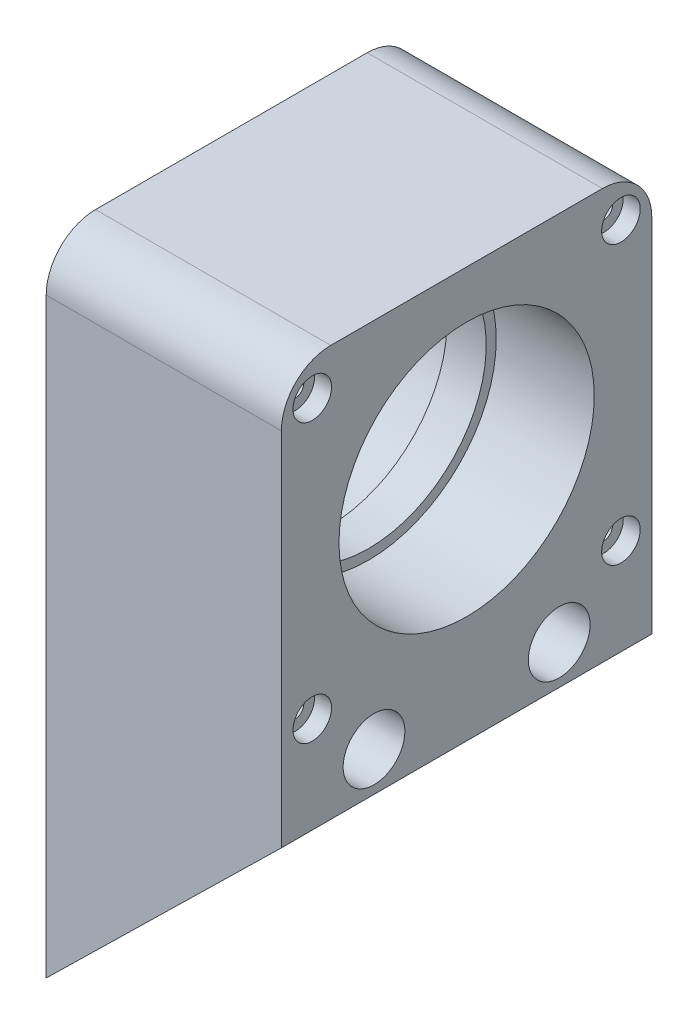
SolidWorks part; units mm, degrees
ref_plane "Front Plane" through (0, 0, 0) normal (0, 0, 1) x (1, 0, 0)
ref_plane "Top Plane" through (0, 0, 0) normal (0, 1, 0) x (1, 0, 0)
ref_plane "Right Plane" through (0, 0, 0) normal (1, 0, 0) x (0, 0, -1)
sketch "Sketch1" plane through (0, 0, 0) normal (0, 0, 1) x (1, 0, 0)
  line L0 (381, 457.2) -> (457.2, 457.2)
  line L1 (457.2, 457.2) -> (457.2, 431.8)
  line L2 (381, 457.2) -> (381, 357.2)
  line L5 (381, 357.2) -> (457.2, 431.8)
  dimension "D1" = 76.2
  dimension "D2" = 100
extrude "Boss-Extrude1" add sketch "Sketch1" along normal blind 120
sketch "Sketch3" plane through (457.2, 0, 0) normal (1, 0, 0) x (0, 0, -1)
  line L1 (-120, 431.8) -> (0, 431.8)
  line L2 (-120, 431.8) -> (-120, 357.2)
  line L3 (-120, 357.2) -> (0, 357.2)
  line L4 (0, 431.8) -> (0, 357.2)
  circle A0 centre (-90, 394.5) radius 4.25
  circle A1 centre (-30, 394.5) radius 4.25
  circle A2 centre (-90, 444.5) radius 4.25
  circle A3 centre (-30, 444.5) radius 4.25
  dimension "D1" = 30
  dimension "D2" = 30
  dimension "D3" = 37.3
  dimension "D4" = 37.3
extrude "Cut-Extrude1" cut sketch "Sketch3" against normal blind 120 contours A1 | A0
sketch "Sketch5" plane through (457.2, 0, 0) normal (1, 0, 0) x (0, 0, -1)
  circle A0 centre (-90, 394.5) radius 10
  circle A1 centre (-30, 394.5) radius 10
  circle A2 centre (-90, 444.5) radius 10
  circle A3 centre (-30, 444.5) radius 10
extrude "Cut-Extrude2" cut sketch "Sketch5" against normal blind 53
sketch "Sketch6" plane through (457.2, 0, 0) normal (1, 0, 0) x (0, 0, -1)
  circle A0 centre (-90, 444.5) radius 4.25
  circle A1 centre (-30, 444.5) radius 4.25
extrude "Cut-Extrude3" cut sketch "Sketch6" against normal blind 103
sketch "Sketch7" plane through (0, 457.2, 0) normal (0, 1, 0) x (1, 0, 0)
  line L1 (381, 0) -> (457.2, 0)
  line L2 (381, 0) -> (381, -120)
  line L3 (381, -120) -> (457.2, -120)
  line L4 (457.2, 0) -> (457.2, -120)
extrude "Boss-Extrude2" add sketch "Sketch7" along normal blind 101.6
sketch "Sketch8" plane through (381, 0, 0) normal (-1, 0, 0) x (0, 0, 1)
  line L0 (120, 457.2) -> (0, 457.2)
  line L1 (120, 558.8) -> (120, 357.2) construction
  line L2 (0, 558.8) -> (0, 357.2) construction
  line L3 (0, 558.8) -> (120, 558.8) construction
  circle A0 centre (60, 508) radius 41.35
  dimension "D1" = 101.6
  dimension "D2" = 50.8
extrude "Cut-Extrude4" cut sketch "Sketch8" against normal blind 31.75 contours A0 region at (381, 508, 60)
sketch "Sketch9" plane through (457.2, 0, 0) normal (1, 0, 0) x (0, 0, -1)
  line L0 (-120, 558.8) -> (0, 558.8) construction
  line L1 (-120, 431.8) -> (-120, 558.8) construction
  circle A0 centre (-60, 508) radius 41.35
  dimension "D1" = 50.8
  dimension "D2" = 60
extrude "Cut-Extrude5" cut sketch "Sketch9" against normal blind 31.75
sketch "Sketch10" plane through (457.2, 0, 0) normal (1, 0, 0) x (0, 0, -1)
  circle A0 centre (-60, 508) radius 38.1
extrude "Cut-Extrude6" cut sketch "Sketch10" against normal blind 76.2
sketch "Sketch13" plane through (0, 558.8, 0) normal (0, 1, 0) x (1, 0, 0)
  line L1 (381, 0) -> (457.2, 0)
  line L2 (381, 0) -> (381, -120)
  line L3 (381, -120) -> (457.2, -120)
  line L4 (457.2, 0) -> (457.2, -120)
extrude "Boss-Extrude3" add sketch "Sketch13" along normal blind 6
sketch "Sketch11" plane through (457.2, 0, 0) normal (1, 0, 0) x (0, 0, -1)
  line L0 (-120, 431.8) -> (-120, 564.8) construction
  line L1 (-110, 553) -> (-10, 553)
  line L2 (-110, 553) -> (-110, 463)
  line L3 (-110, 463) -> (-10, 463)
  line L4 (-10, 553) -> (-10, 463)
  line L5 (0, 431.8) -> (0, 564.8) construction
  circle A0 centre (-60, 508) radius 5.3331
  circle A1 centre (-110, 553) radius 2.75
  circle A2 centre (-10, 553) radius 2.75
  circle A3 centre (-10, 463) radius 2.75
  circle A4 centre (-110, 463) radius 2.75
  dimension "D1" = 10
  dimension "D2" = 10
  dimension "D3" = 45
  dimension "D4" = 90
extrude "Cut-Extrude7" cut sketch "Sketch11" against normal blind 84.4 contours L1 A1 L2 | L2 A1 L1 | L4 A2 L1 | L1 A2 L4 | L3 A3 L4 | L4 A3 L3 | L2 A4 L3 | L3 A4 L2 region at (457.2, 553.389, 110.389) region at (457.2, 551.8329, 108.8329) region at (457.2, 553.389, 9.611) region at (457.2, 551.8329, 11.1671) region at (457.2, 464.1671, 108.8329) region at (457.2, 462.611, 110.389) region at (457.2, 462.611, 9.611) region at (457.2, 464.1671, 11.1671)
sketch "Sketch12" plane through (457.2, 0, 0) normal (1, 0, 0) x (0, 0, -1)
  circle A0 centre (-110, 553) radius 6.25
  circle A1 centre (-10, 553) radius 6.25
  circle A2 centre (-10, 463) radius 6.25
  circle A3 centre (-110, 463) radius 6.25
extrude "Cut-Extrude8" cut sketch "Sketch12" against normal blind 5.5
fillet "Fillet1" radius 16 2 edges at (419.1, 564.8, 0) (419.1, 564.8, 120)
